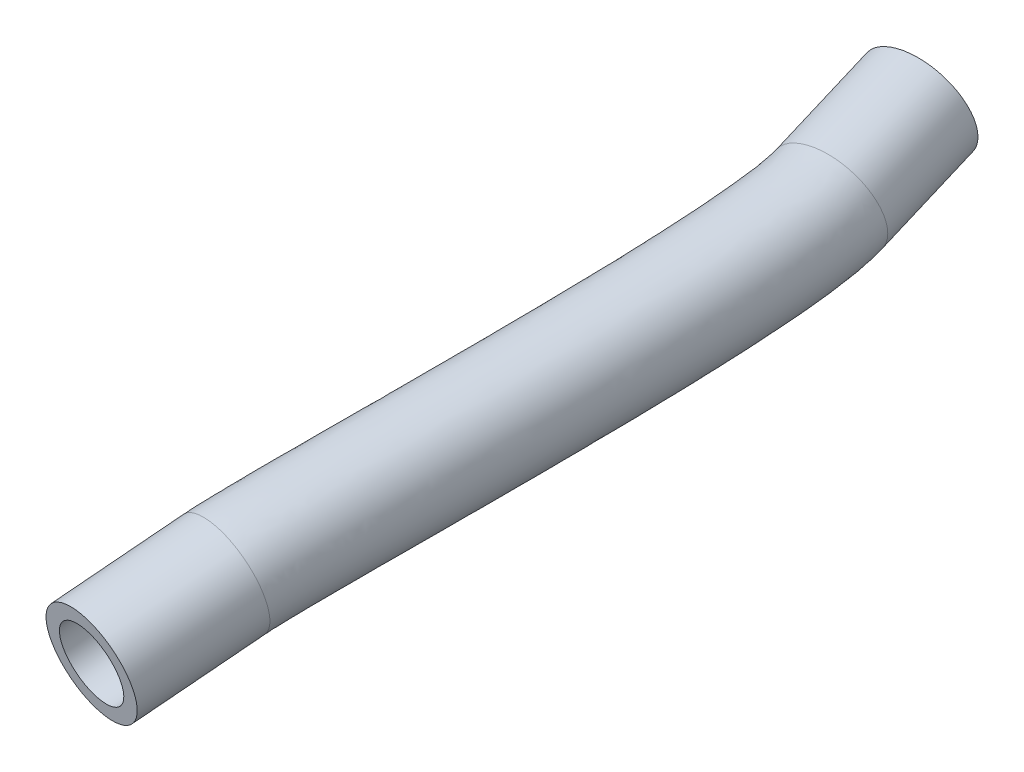
SolidWorks part; units mm, degrees
material "Silicon Rubber"
ref_plane "X-Y Datum" through (0, 0, 0) normal (0, 0, 1) x (1, 0, 0)
ref_plane "X-Z Datum" through (0, 0, 0) normal (0, 1, 0) x (1, 0, 0)
ref_plane "Y-Z Datum" through (0, 0, 0) normal (1, 0, 0) x (0, 0, -1)
sketch3d "3DSketch1"
  line L0 (-1498.6578, -955.5583, 549.891) -> (-1495.4514, -962.464, 576.8359)
  line L1 (-1508.718, -981.6748, 722.8521) -> (-1513.0137, -988.9022, 753.4687)
  line L2 (-1508.718, -981.6748, 722.8521) -> (-1516.437, -994.6615, 777.8667) construction
  line L3 (-1498.5433, -955.8049, 550.8533) -> (-1495.4514, -962.464, 576.8359) construction
  circle A0 centre (-1498.5433, -955.8049, 550.8533) radius 10 construction
  circle A1 centre (-1495.4514, -962.464, 576.8359) radius 8 construction
  circle A4 centre (-1498.5433, -955.8049, 550.8533) radius 10 construction
  circle A5 centre (-1495.4514, -962.464, 576.8359) radius 8 construction
  circle A13 centre (-1508.718, -981.6748, 722.8521) radius 7.366 construction
  circle A14 centre (-1516.437, -994.6615, 777.8667) radius 8.2959 construction
  circle A15 centre (-1508.718, -981.6748, 722.8521) radius 7.366 construction
  circle A16 centre (-1516.437, -994.6615, 777.8667) radius 8.2959 construction
  circle A17 centre (-1498.6578, -955.5583, 549.891) radius 11 construction
  circle A18 centre (-1498.6578, -955.5583, 549.891) radius 11 construction
  spline S0 degree 3 poles (-1495.4514, -962.464, 576.8359) (-1492.7736, -968.2312, 599.3389) (-1506.2132, -977.4607, 705.0003) (-1508.718, -981.6748, 722.8521) knots 0 0 0 0 1 1 1 1
  point P5 (-1507.7214, -979.9981, 715.7491)
  point P10 (-1515.3145, -992.7731, 769.867)
  point P12 (-1507.7214, -979.9981, 715.7491)
  point P14 (-1515.3145, -992.7731, 769.867)
  point P16 (-1497.3982, -958.2712, 560.4765)
  point P19 (-1494.5353, -964.437, 584.5345)
  point P21 (-1497.3982, -958.2712, 560.4765)
  point P23 (-1494.5353, -964.437, 584.5345)
  point P26 (-1497.3982, -958.2712, 560.4765)
  point P28 (-1497.3982, -958.2712, 560.4765)
  dimension "D1" = 31.75
sweep "Sweep1" add path "3DSketch1" circular profile diameter 26.9875 parameters "D3"=26.9875
sweep "Cut-Sweep1" cut path "3DSketch1<2>" circular profile diameter 19.05 parameters "D3"=19.05
sketch3d "3DSketch1<2>" same geometry as "3DSketch1"
